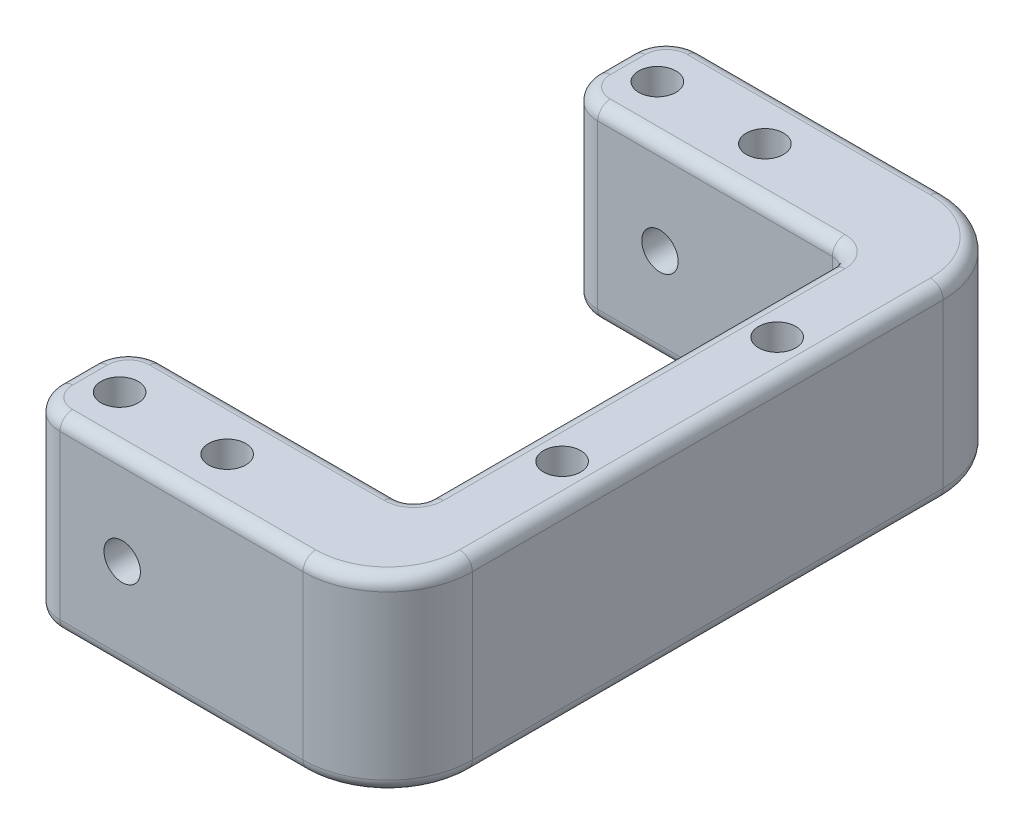
SolidWorks part; units mm, degrees
ref_plane "Front Plane" through (0, 0, 0) normal (0, 0, 1) x (1, 0, 0)
ref_plane "Top Plane" through (0, 0, 0) normal (0, 1, 0) x (1, 0, 0)
ref_plane "Right Plane" through (0, 0, 0) normal (1, 0, 0) x (0, 0, -1)
sketch "Sketch1" plane through (0, 0, 0) normal (0, 1, 0) x (1, 0, 0)
  line L1 (-5, 6.0452) -> (28.7, 6.0452)
  line L2 (-5, 6.0452) -> (-5, -6.0452)
  line L3 (-5, -6.0452) -> (37.7, -6.0452)
  line L8 (28.7, 6.0452) -> (28.7, 57.4548)
  line L9 (37.7, 69.5452) -> (-5, 69.5452)
  line L10 (37.7, 69.5452) -> (37.7, -6.0452)
  line L11 (28.7, 57.4548) -> (-5, 57.4548)
  line L12 (-5, 69.5452) -> (-5, 57.4548)
  circle A0 centre (0, 0) radius 2.2
  circle A1 centre (12.7, 0) radius 2.2
  circle A2 centre (12.7, 63.5) radius 2.2
  circle A3 centre (0, 63.5) radius 2.2
  circle A4 centre (33.2, 44.45) radius 2.2
  circle A5 centre (33.2, 19.05) radius 2.2
  point P9 (-5, 63.5)
  point P19 (28.7, 57.4548)
  point P20 (28.7, 6.0452)
  point P24 (28.7, 31.75)
  point P27 (-5, 0)
  dimension "D1" = 4.4
  dimension "D11" = 4.5
  dimension "D2" = 12.7
  dimension "D3" = 63.5
  dimension "D4" = 6.0452
  dimension "D5" = 6.0452
  dimension "D6" = 9
  dimension "D7" = 5
  dimension "D8" = 16
  dimension "D9" = 25.4
  dimension "D10" = 12.7
extrude "Boss-Extrude1" add sketch "Sketch1" along normal blind 22.2504 contours L9 L12 L11 L8 L1 L2 L3 L10 A3 A2 A1 A0 region at (11.85, 0, -5.177)
fillet "Fillet1" radius 10 2 edges at (37.7, 11.1252, -69.5452) (37.7, 11.1252, 6.0452)
fillet "Fillet2" radius 2 2 edges at (28.7, 11.1252, -57.4548) (28.7, 11.1252, -6.0452)
fillet "Fillet3" radius 4 4 edges at (-5, 11.1252, -69.5452) (-5, 11.1252, -57.4548) (-5, 11.1252, -6.0452) (-5, 11.1252, 6.0452)
fillet "Fillet4" radius 1.5 32 edges at (-3.8284, 0, -4.8736) (12.85, 0, -6.0452) (28.1142, 0, -6.631) (28.7, 0, -31.75) (28.1142, 0, -56.869) (12.85, 0, -57.4548) (-3.8284, 0, -58.6264) (-3.8284, 0, -68.3736) (13.35, 0, -69.5452) (34.7711, 0, -66.6163) (37.7, 0, -31.75) (-3.8284, 22.2504, -4.8736) (12.85, 22.2504, -6.0452) (28.1142, 22.2504, -6.631) (28.7, 22.2504, -31.75) (28.1142, 22.2504, -56.869) (12.85, 22.2504, -57.4548) (-3.8284, 22.2504, -58.6264) (-3.8284, 22.2504, -68.3736) (13.35, 22.2504, -69.5452) (34.7711, 22.2504, -66.6163) (37.7, 22.2504, -31.75) (-3.8284, 0, 4.8736) (34.7711, 0, 3.1163) (-3.8284, 22.2504, 4.8736) (34.7711, 22.2504, 3.1163) (13.35, 0, 6.0452) (13.35, 22.2504, 6.0452) (-5, 0, 0) (-5, 0, -63.5) (-5, 22.2504, 0) (-5, 22.2504, -63.5)
sketch "Sketch2" plane through (0, 0, 6.0452) normal (0, 0, 1) x (1, 0, 0)
  line L0 (14.9, 22.2504) -> (10.5, 22.2504) construction
  line L1 (2.2, 22.2504) -> (-2.2, 22.2504) construction
  line L2 (14.9, 22.2504) -> (10.5, 22.2504)
  line L3 (2.2, 22.2504) -> (-2.2, 22.2504)
  line L4 (-1, 20.7504) -> (-1, 1.5) construction
  line L5 (-1, 20.7504) -> (-1, 1.5)
  circle A0 centre (6.35, 11.1252) radius 2.15
  point P4 (12.7, 22.2504)
  point P6 (0, 22.2504)
  point P10 (-1, 11.1252)
  dimension "D1" = 4.3
  dimension "D2" = 6.35
extrude "Cut-Extrude1" cut sketch "Sketch2" against normal through all contours A0 region at (6.35, 11.1252, 6.0452)
